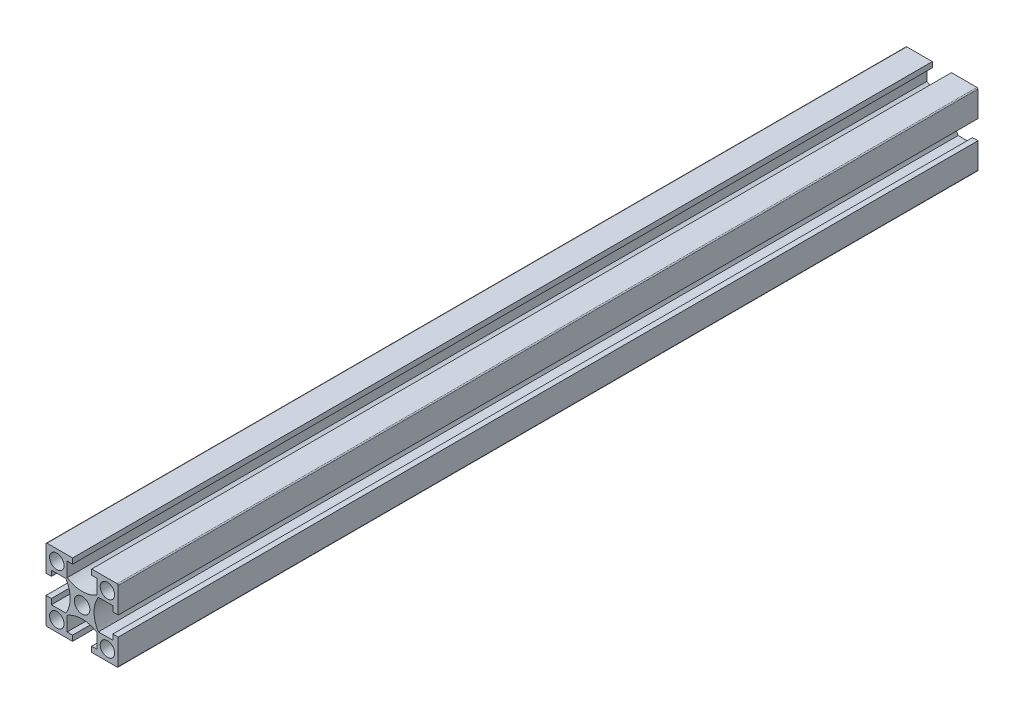
SolidWorks part; units mm, degrees
material "3.0255 (EN-AW 1350A)"
ref_plane "정면" through (0, 0, 0) normal (0, 0, 1) x (1, 0, 0)
ref_plane "윗면" through (0, 0, 0) normal (0, 1, 0) x (1, 0, 0)
ref_plane "우측면" through (0, 0, 0) normal (1, 0, 0) x (0, 0, -1)
sketch "스케치1" plane through (0, 0, 0) normal (0, 0, 1) x (1, 0, 0)
  line L0 (0, 32.0265) -> (0, -31.6588) construction
  line L1 (-10, 10) -> (-10, -10)
  line L2 (-10, 10) -> (10, 10)
  line L3 (-10, 2.65) -> (-8.5, 2.65)
  line L4 (13.6618, 0) -> (-11.6993, 0) construction
  line L5 (-8.5, 2.65) -> (-8.5, 4.15)
  line L6 (-8.5, 4.15) -> (-4.5032, 4.15)
  line L7 (-10, -2.65) -> (-8.5, -2.65)
  line L8 (-8.5, -2.65) -> (-8.5, -4.15)
  line L9 (-8.5, -4.15) -> (-4.5032, -4.15)
  line L10 (-10, -10) -> (10, -10)
  line L11 (10, 10) -> (10, -10)
  circle A0 centre (-7, 7) radius 2
  circle A1 centre (-7, -7) radius 2
  arc A2 (-4.5032, 4.15) -> (-4.5032, -4.15) centre (-11.0587, 0) cw
  circle A3 centre (0, 0) radius 2.15
  circle A4 centre (7, 7) radius 2
  circle A5 centre (7, -7) radius 2
  point P21 (-10, 0)
  point P23 (-3.3, 0)
  point P31 (0, -10)
  point P32 (0, 10)
  dimension "D3" = 4
  dimension "D9" = 6.7
  dimension "D10" = 4.3
  dimension "D11" = 7.7587
  dimension "D1" = 20
  dimension "D2" = 20
  dimension "D4" = 14
  dimension "D5" = 14
  dimension "D6" = 5.3
  dimension "D7" = 8.3
  dimension "D8" = 1.5
extrude "보스-돌출1" add sketch "스케치1" along normal blind 238 contours A0 | A4 | A3 | A5 | A1 | A2 L6 L5 L3 L1 L7 L8 L9 | L2 L11 L10 L1 region at (-6.6069, 0, 0) region at (-7, 7, 0) region at (-7, -7, 0) region at (0, 0, 0) region at (7, 7, 0) region at (7, -7, 0)
extrude "컷-돌출1" cut sketch "스케치1<3>" along normal up to next contours A2 L6 L5 L3 L1 L7 L8 L9 region at (-6.6069, 0, 0)
sketch "스케치1<3>" plane through (0, 0, 0) normal (0, 0, 1) x (1, 0, 0) same geometry as "스케치1"
pattern_circular "원형 패턴1" count 4 over 360 about axis through (0, 0, 238) along (0, 0, -1) of "컷-돌출1" reverse direction yes
fillet "필렛1" radius 0.3 4 edges at (10, -10, 119) (-10, -10, 119) (-10, 10, 119) (10, 10, 119)
